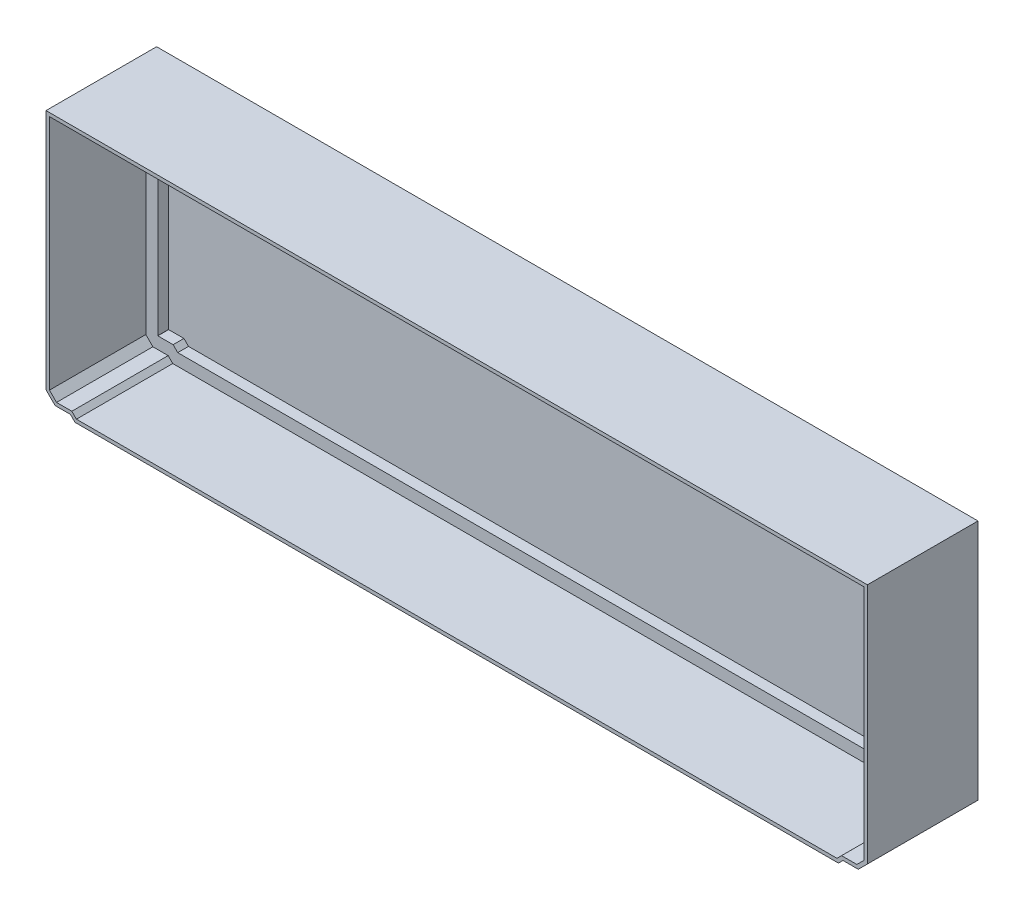
SolidWorks part; units mm, degrees
ref_plane "Přední rovina" through (0, 0, 0) normal (0, 0, 1) x (1, 0, 0)
ref_plane "Horní rovina" through (0, 0, 0) normal (0, 1, 0) x (1, 0, 0)
ref_plane "Pravá rovina" through (0, 0, 0) normal (1, 0, 0) x (0, 0, -1)
sketch "Skica3" plane through (0, 0, 0) normal (0, 0, 1) x (1, 0, 0)
  line L0 (0, 0) -> (415.1053, 0) construction
  line L1 (415.1053, 0) -> (416.6927, -1.5875) construction
  line L2 (416.6927, -1.5875) -> (416.6927, -119.8485) construction
  line L3 (0, 0) -> (-1.5875, -1.5875) construction
  line L4 (-1.5875, -1.5875) -> (-1.5875, -119.8485) construction
  line L5 (-1.5875, -119.8485) -> (0.7934, -122.2292) construction
  line L6 (0.7934, -122.2292) -> (8.7304, -122.2292) construction
  line L7 (8.7304, -122.2292) -> (11.1113, -124.61) construction
  line L8 (11.1113, -124.61) -> (403.9933, -124.61) construction
  line L9 (403.9933, -124.61) -> (406.3744, -122.2294) construction
  line L10 (406.3744, -122.2294) -> (414.3114, -122.2294) construction
  line L11 (416.6927, -119.8485) -> (414.3114, -122.2294) construction
  line L12 (2.4125, -4) -> (412.6927, -4)
  line L13 (412.6927, -4) -> (412.6927, -4)
  line L14 (412.6927, -4) -> (412.6927, -118.1914)
  line L15 (412.6927, -118.1914) -> (412.6547, -118.2294)
  line L16 (404.7177, -118.2294) -> (412.6547, -118.2294)
  line L17 (402.3367, -120.61) -> (404.7177, -118.2294)
  line L18 (12.7681, -120.61) -> (402.3367, -120.61)
  line L19 (10.3872, -118.2292) -> (12.7681, -120.61)
  line L20 (2.4502, -118.2292) -> (10.3872, -118.2292)
  line L21 (2.4125, -118.1915) -> (2.4502, -118.2292)
  line L22 (2.4125, -4) -> (2.4125, -118.1915)
  line L23 (2.4125, -4) -> (2.4125, -4)
  line L24 (-1.5875, -119.8485) -> (415.1053, 0) construction
  line L26 (0, 0) -> (416.6927, -119.8485) construction
  dimension "D1" = 135
  dimension "D2" = 135
  dimension "D3" = 4
  dimension "D4" = 2.245
  dimension "D5" = 2.245
  dimension "D6" = 118.261
  dimension "D7" = 118.261
  dimension "D8" = 3.367
  dimension "D9" = 7.937
  dimension "D10" = 3.367
  dimension "D11" = 392.882
  dimension "D12" = 3.367
  dimension "D13" = 7.937
  dimension "D14" = 3.3674
extrude "Přidat vysunutím1" add sketch "Skica3" along normal blind 5.6
shell "Skořepina1" thickness 1.8 removed face at (207.5525, -95.852, 5.6) outward yes
sketch "Skica7" plane through (0, 0, 5.6) normal (0, 0, 1) x (1, 0, 0)
  line L20 (-5.5875, 4) -> (-5.5875, -121.5054)
  line L21 (-5.5875, -121.5054) -> (-0.8634, -126.2292)
  line L22 (-0.8634, -126.2292) -> (7.0736, -126.2292)
  line L23 (7.0736, -126.2292) -> (9.4545, -128.61)
  line L24 (9.4545, -128.61) -> (405.65, -128.61)
  line L25 (405.65, -128.61) -> (408.031, -126.2294)
  line L26 (408.031, -126.2294) -> (415.968, -126.2294)
  line L27 (415.968, -126.2294) -> (420.6927, -121.5055)
  line L28 (420.6927, -121.5055) -> (420.6927, 4)
  line L29 (420.6927, 4) -> (-5.5875, 4)
  line L30 (-5.5875, 4) -> (-5.5875, -121.5054)
  line L31 (-5.5875, -121.5054) -> (-0.8634, -126.2292)
  line L32 (-0.8634, -126.2292) -> (7.0736, -126.2292)
  line L33 (7.0736, -126.2292) -> (9.4545, -128.61)
  line L34 (9.4545, -128.61) -> (405.65, -128.61)
  line L35 (405.65, -128.61) -> (408.031, -126.2294)
  line L36 (408.031, -126.2294) -> (415.968, -126.2294)
  line L37 (415.968, -126.2294) -> (420.6927, -121.5055)
  line L38 (420.6927, -121.5055) -> (420.6927, 4)
  line L39 (420.6927, 4) -> (-5.5875, 4)
  line L40 (-3.7875, 2.2) -> (-3.7875, -120.7598)
  line L41 (-3.7875, -120.7598) -> (-0.1178, -124.4292)
  line L42 (-0.1178, -124.4292) -> (7.8192, -124.4292)
  line L43 (7.8192, -124.4292) -> (10.2001, -126.81)
  line L44 (10.2001, -126.81) -> (404.9045, -126.81)
  line L45 (404.9045, -126.81) -> (407.2855, -124.4294)
  line L46 (407.2855, -124.4294) -> (415.2225, -124.4294)
  line L47 (415.2225, -124.4294) -> (418.8927, -120.7598)
  line L48 (418.8927, -120.7598) -> (418.8927, 2.2)
  line L49 (418.8927, 2.2) -> (-3.7875, 2.2)
  line L50 (-3.7875, 2.2) -> (-3.7875, -120.7598)
  line L51 (-3.7875, -120.7598) -> (-0.1178, -124.4292)
  line L52 (-0.1178, -124.4292) -> (7.8192, -124.4292)
  line L53 (7.8192, -124.4292) -> (10.2001, -126.81)
  line L54 (10.2001, -126.81) -> (404.9045, -126.81)
  line L55 (404.9045, -126.81) -> (407.2855, -124.4294)
  line L56 (407.2855, -124.4294) -> (415.2225, -124.4294)
  line L57 (415.2225, -124.4294) -> (418.8927, -120.7598)
  line L58 (418.8927, -120.7598) -> (418.8927, 2.2)
  line L59 (418.8927, 2.2) -> (-3.7875, 2.2)
  point P0 (0, 0)
  dimension "D2" = 4.4
  dimension "D1" = 6.2
extrude "Přidat vysunutím3" add sketch "Skica7" along normal blind 50 separate body
sketch "Skica8" plane through (0, 0, 5.6) normal (0, 0, -1) x (-1, 0, 0)
  line L0 (-420.6927, 4) -> (5.5875, 4)
  line L1 (5.5875, 4) -> (5.5875, -121.5054)
  line L2 (5.5875, 4) -> (5.5875, -121.5054) construction
  line L3 (5.5875, -121.5054) -> (0.8634, -126.2292)
  line L4 (0.8634, -126.2292) -> (-7.0736, -126.2292)
  line L5 (-7.0736, -126.2292) -> (-9.4545, -128.61)
  line L6 (-9.4545, -128.61) -> (-405.65, -128.61)
  line L7 (-405.65, -128.61) -> (-408.031, -126.2294)
  line L8 (-408.031, -126.2294) -> (-415.968, -126.2294)
  line L9 (-415.968, -126.2294) -> (-420.6927, -121.5055)
  line L10 (-420.6927, -121.5055) -> (-420.6927, 4)
  line L11 (-0.6125, -2.2) -> (-0.6125, -118.9371)
  line L12 (-414.4927, -2.2) -> (-0.6125, -2.2) construction
  line L13 (-0.6125, -2.2) -> (-0.6125, -118.9371) construction
  line L14 (-0.6125, -118.9371) -> (-1.7047, -120.0292)
  line L15 (-1.7047, -120.0292) -> (-9.6417, -120.0292)
  line L16 (-9.6417, -120.0292) -> (-12.0226, -122.41)
  line L17 (-12.0226, -122.41) -> (-403.0822, -122.41)
  line L18 (-403.0822, -122.41) -> (-405.4632, -120.0294)
  line L19 (-405.4632, -120.0294) -> (-413.4002, -120.0294) construction
  line L20 (-405.4632, -120.0294) -> (-413.4002, -120.0294)
  line L21 (-413.4002, -120.0294) -> (-414.4927, -118.9371) construction
  line L22 (-413.4002, -120.0294) -> (-414.4927, -118.9371)
  line L23 (-414.4927, -118.9371) -> (-414.4927, -2.2)
  line L24 (-414.4927, -2.2) -> (-0.6125, -2.2)
extrude "Přidat vysunutím4" add sketch "Skica8" along normal up to surface (7.4 mm away) up to face at (207.5525, -96.7211, -1.8)
